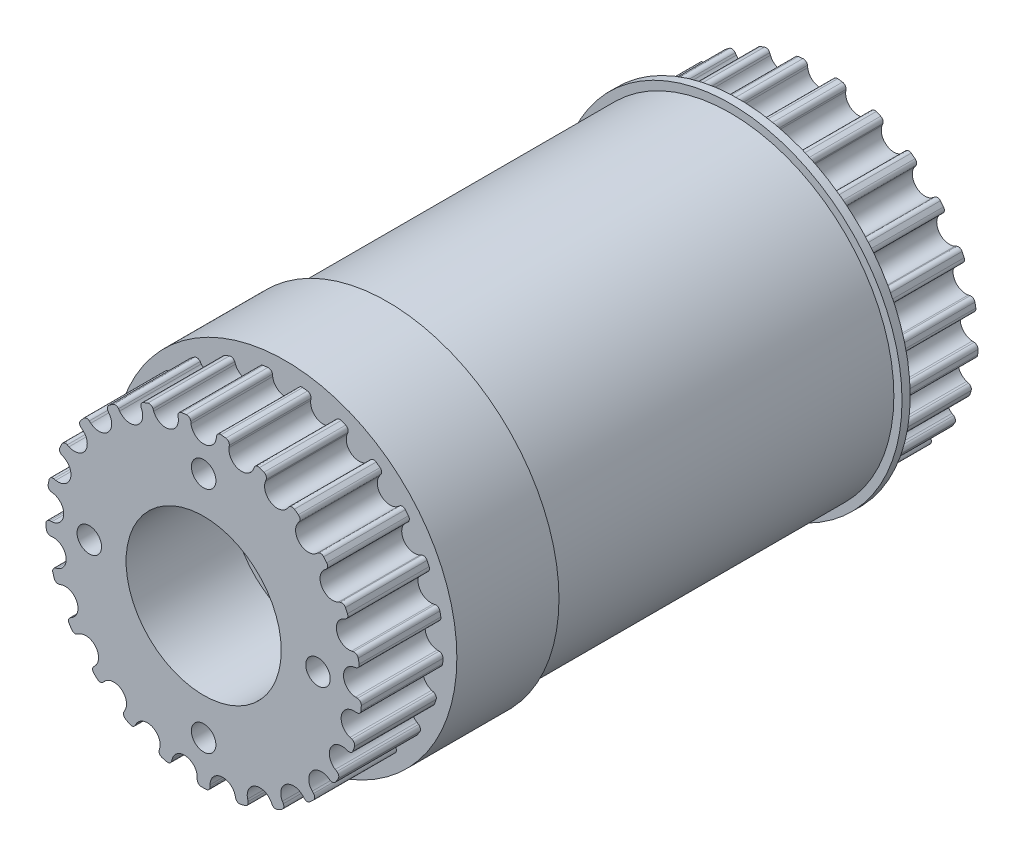
SolidWorks part; units mm, degrees
material "6061 合金"
ref_plane "前视基准面" through (0, 0, 0) normal (0, 0, 1) x (1, 0, 0)
ref_plane "上视基准面" through (0, 0, 0) normal (0, 1, 0) x (1, 0, 0)
ref_plane "右视基准面" through (0, 0, 0) normal (1, 0, 0) x (0, 0, -1)
other "Configuration Table"
sketch "草图1" plane through (0, 0, 0) normal (0, 0, 1) x (1, 0, 0)
  circle A0 centre (0, 0) radius 19.8944
  dimension "P.D" = 39.7887
extrude "凸台-拉伸1" add sketch "草图1" along normal blind 75.5
sketch "草图2" plane through (0, 0, 75.5) normal (0, 0, 1) x (1, 0, 0)
  line L0 (0, 19.8944) -> (0, 19.3224) construction
  line L1 (0, 19.3224) -> (0, 0) construction
  line L2 (1.5774, 18.7687) -> (1.5484, 18.5323)
  line L3 (2.4934, 19.7375) -> (2.4217, 19.17)
  line L4 (-2.4934, 19.7375) -> (-2.4217, 19.17)
  line L5 (-1.5774, 18.7687) -> (-1.5484, 18.5323)
  circle A0 centre (0, 0) radius 19.8944 construction
  arc A1 (2.4934, 19.7375) -> (-2.4934, 19.7375) centre (0, 0) ccw
  circle A2 centre (0, 0) radius 19.3224 construction
  arc A3 (-1.5484, 18.5323) -> (1.5484, 18.5323) centre (0, 18.7224) ccw
  arc A4 (2.1288, 19.2047) -> (2.4217, 19.17) centre (0, 0) cw
  arc A5 (1.5774, 18.7687) -> (2.1288, 19.2047) centre (2.0737, 18.7078) cw
  arc A6 (-1.5774, 18.7687) -> (-2.1288, 19.2047) centre (-2.0737, 18.7078) ccw
  arc A7 (-2.1288, 19.2047) -> (-2.4217, 19.17) centre (0, 0) ccw
  point P16 (1.6369, 19.2529)
  point P21 (0, 17.1624)
  dimension "R" = 1.56
  dimension "D3" = 0.5
  dimension "D1" = 7.2
  dimension "D2" = 7
  dimension "H_g" = 2.16
  dimension "delta" = 0.572
extrude "切除-拉伸1" cut sketch "草图2" against normal through all
pattern_circular "阵列(圆周)1" count 25 over 360 about axis through (0, 0, 75.5) along (0, 0, -1) of "切除-拉伸1" reverse direction yes
ref_plane "基准面1" through (0, 0, 10) normal (0, 0, -1) x (-1, 0, 0)
ref_plane "基准面2" through (0, 0, 11) normal (0, 0, -1) x (-1, 0, 0)
ref_plane "基准面3" through (0, 0, 53) normal (0, 0, -1) x (-1, 0, 0)
ref_plane "基准面4" through (0, 0, 57.5) normal (0, 0, -1) x (-1, 0, 0)
ref_plane "基准面5" through (0, 0, 58.5) normal (0, 0, -1) x (-1, 0, 0)
sketch "草图3" plane through (0, 0, 10) normal (0, 0, -1) x (-1, 0, 0)
  circle A0 centre (0, 0) radius 21
  dimension "D1" = 42
extrude "凸台-拉伸2" add sketch "草图3" against normal up to surface (1 mm away) up to plane "基准面2"
sketch "草图4" plane through (0, 0, 11) normal (0, 0, -1) x (-1, 0, 0)
  circle A0 centre (0, 0) radius 20
  dimension "D1" = 40
extrude "凸台-拉伸3" add sketch "草图4" against normal up to surface (42 mm away) up to plane "基准面3"
sketch "草图5" plane through (0, 0, 53) normal (0, 0, -1) x (-1, 0, 0)
  circle A0 centre (0, 0) radius 21 construction
  circle A1 centre (0, 0) radius 21
extrude "凸台-拉伸4" add sketch "草图5" against normal blind 12.5
sketch "草图6" plane through (0, 0, 0) normal (0, 0, -1) x (-1, 0, 0)
  circle A0 centre (0, 0) radius 5.2
  circle A1 centre (0, 0) radius 9.5
  dimension "D1" = 10.4
  dimension "D2" = 19
extrude "切除-拉伸2" cut sketch "草图6" against normal through all contours A0
extrude "切除-拉伸3" cut sketch "草图6<3>" against normal blind 13
sketch "草图6<3>" plane through (0, 0, 0) normal (0, 0, -1) x (-1, 0, 0) same geometry as "草图6"
extrude "切除-拉伸4" cut sketch "草图6<4>" along normal blind 13 from surface starting at face at (-5.2, 0, 75.5)
sketch "草图6<4>" plane through (0, 0, 0) normal (0, 0, -1) x (-1, 0, 0) same geometry as "草图6"
sketch "草图7" plane through (0, 0, 0) normal (0, 0, -1) x (-1, 0, 0)
  line L0 (-14, 0) -> (14, 0) construction
  line L1 (0, -14) -> (0, 14) construction
  circle A0 centre (14, 0) radius 1.5
  circle A1 centre (14, 0) radius 1.5
  circle A2 centre (14, 0) radius 1.5
  circle A3 centre (14, 0) radius 1.5
  circle A10 centre (0, -14) radius 1.5
  circle A11 centre (-14, 0) radius 1.5
  circle A12 centre (0, 14) radius 1.5
  dimension "D1" = 3
  dimension "D2" = 14
  dimension "D5" = 14
  dimension "D4" = 14
  dimension "D3" = 14
extrude "切除-拉伸5" cut sketch "草图7" against normal through all contours A12 | A0 | A10 | A11 region at (-14, 0, 0) region at (0, -14, 0) region at (14, 0, 0) region at (0, 14, 0)
equation "\"P\"= 5'（勿动）"
equation "\"N\"= 25'齿数（5M不小于13）"
equation "\"H\"= 75.5'齿厚（一般为带宽+2）"
equation "\"R_t\"= 0.5'齿槽圆角（通常无需修改）"
equation "\"P.D@草图1\"= \"P\" * \"N\" / pi'节径"
equation "\"D1@凸台-拉伸1\"=\"H\""
equation "\"D1@草图2\"= 180 / \"N\"'作者：wister"
equation "\"R@草图2\"= 1.56'齿顶圆角"
equation "\"D3@草图2\"=\"R_t\""
equation "\"D1@阵列(圆周)1\"=\"N\""
equation "\"H_g@草图2\"= 2.16'齿槽深"
equation "\"delta@草图2\"= 1.144 / 2'节顶距"
